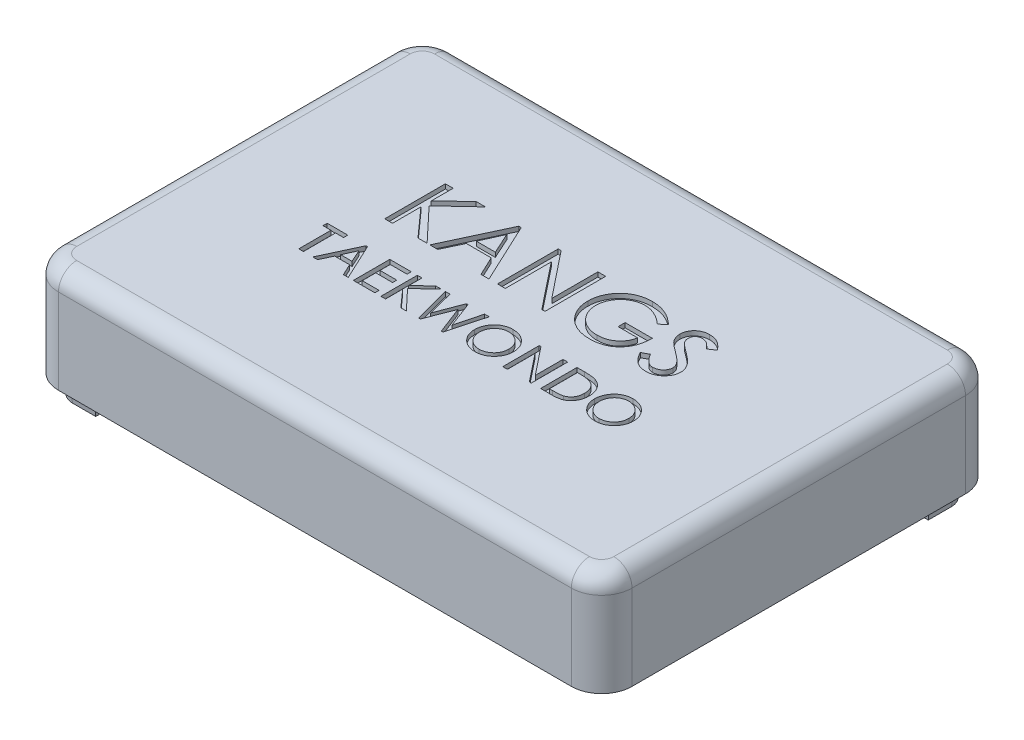
SolidWorks part; units mm, degrees
ref_plane "Front Plane" through (0, 0, 0) normal (0, 0, 1) x (1, 0, 0)
ref_plane "Top Plane" through (0, 0, 0) normal (0, 1, 0) x (1, 0, 0)
ref_plane "Right Plane" through (0, 0, 0) normal (1, 0, 0) x (0, 0, -1)
sketch "Sketch1" plane through (0, 0, 0) normal (0, 1, 0) x (1, 0, 0)
  line L0 (-44.1692, -23.3779) -> (-44.1692, 31.5679)
  line L1 (-39.1692, -26.3779) -> (45.3308, -26.3779)
  line L2 (-42.1692, -23.3779) -> (-42.1692, 31.5679)
  line L3 (-39.1692, 34.5679) -> (45.3308, 34.5679)
  line L4 (48.3308, -23.3779) -> (48.3308, 31.5679)
  line L5 (-42.1692, -26.3779) -> (48.3308, 34.5679) construction
  line L6 (-42.1692, 34.5679) -> (48.3308, -26.3779) construction
  line L7 (-39.1692, 36.5679) -> (45.3308, 36.5679)
  line L8 (50.3308, -23.3779) -> (50.3308, 31.5679)
  line L9 (-39.1692, -28.3779) -> (45.3308, -28.3779)
  line L10 (-44.1692, -5.0821) -> (-44.1692, -18.2821) construction
  line L11 (45.3308, 12.7179) -> (45.3308, 1.7179) construction
  line L12 (-9.4142, 36.5679) -> (3.8358, 36.5679) construction
  line L13 (-33.1692, -23.3779) -> (42.8308, -23.3779) construction
  arc A0 (45.3308, -26.3779) -> (48.3308, -23.3779) centre (45.3308, -23.3779) ccw
  arc A1 (-39.1692, -26.3779) -> (-42.1692, -23.3779) centre (-39.1692, -23.3779) cw
  arc A2 (-42.1692, 31.5679) -> (-39.1692, 34.5679) centre (-39.1692, 31.5679) cw
  arc A3 (45.3308, 34.5679) -> (48.3308, 31.5679) centre (45.3308, 31.5679) cw
  arc A4 (-44.1692, 31.5679) -> (-39.1692, 36.5679) centre (-39.1692, 31.5679) cw
  arc A5 (45.3308, 36.5679) -> (50.3308, 31.5679) centre (45.3308, 31.5679) cw
  arc A6 (45.3308, -28.3779) -> (50.3308, -23.3779) centre (45.3308, -23.3779) ccw
  arc A7 (-39.1692, -28.3779) -> (-44.1692, -23.3779) centre (-39.1692, -23.3779) cw
  point P0 (0, 0)
  dimension "D1" = 3
  dimension "D3" = 3
  dimension "D4" = 3
  dimension "D2" = 2
extrude "Boss-Extrude1" add sketch "Sketch1" along normal blind 1.5 contours A7 L9 A6 L8 A5 L7 A4 L0 L3 A3 L4 A0 L1 A1 L2 A2 | L3 A3 L4 A0 L1 A1 L2 A2 region at (-43.0226, 0, -4.095)
extrude "Boss-Extrude2" add sketch "Sketch1<3>" against normal up to surface (15.53 mm away)
sketch "Sketch1<3>" plane through (0, 0, 0) normal (0, 1, 0) x (1, 0, 0) same geometry as "Sketch1"
sketch "Sketch2" plane through (0, 0, -36.5679) normal (0, 0, -1) x (-1, 0, 0)
  line L5 (-34.8158, -2) -> (25.1542, -2)
  line L6 (-34.8158, -2) -> (-34.8158, -16.03)
  line L7 (-34.8158, -16.03) -> (25.1542, -16.03)
  line L30 (25.1542, -2) -> (25.1542, -16.03)
  line L36 (-21.0658, -3) -> (-34.3158, -3) construction
  line L37 (-34.3158, -15.53) -> (-34.3158, -3) construction
  line L40 (-21.0658, -15.53) -> (-34.3158, -15.53) construction
  line L41 (24.6542, -15.53) -> (24.6542, -3) construction
  dimension "D2" = 1
  dimension "D3" = 0.5
  dimension "D6" = 0.5
  dimension "D1" = 0.5
extrude "Cut-Extrude1" cut sketch "Sketch2" against normal up to next
sketch "Sketch3" plane through (0, 0, 0) normal (0, -1, 0) x (1, 0, 0)
  line L0 (-34.8337, -30.7679) -> (-38.3692, -27.2324)
  line L1 (-38.3692, 19.0424) -> (-34.8337, 22.5779)
  line L2 (40.9953, -30.7679) -> (44.5308, -27.2324)
  line L3 (45.3308, -34.7679) -> (40.9953, -34.7679)
  line L4 (40.9953, -34.7679) -> (40.9953, -30.7679)
  line L5 (48.5308, -31.5679) -> (48.5308, -27.2324)
  line L6 (48.5308, -27.2324) -> (44.5308, -27.2324)
  line L7 (-39.1692, -34.7679) -> (-34.8337, -34.7679)
  line L8 (-34.8337, -34.7679) -> (-34.8337, -30.7679)
  line L9 (-42.3692, -31.5679) -> (-42.3692, -27.2324)
  line L10 (-42.3692, -27.2324) -> (-38.3692, -27.2324)
  line L11 (-42.3692, 23.3779) -> (-42.3692, 19.0424)
  line L12 (-42.3692, 19.0424) -> (-38.3692, 19.0424)
  line L13 (-34.8337, 22.5779) -> (-34.8337, 26.5779)
  line L14 (-34.8337, 26.5779) -> (-39.1692, 26.5779)
  arc A0 (48.5308, -31.5679) -> (45.3308, -34.7679) centre (45.3308, -31.5679) cw
  arc A1 (45.3308, -34.5679) -> (48.3308, -31.5679) centre (45.3308, -31.5679) ccw construction
  arc A3 (-39.1692, -34.7679) -> (-42.3692, -31.5679) centre (-39.1692, -31.5679) cw
  arc A4 (-42.1692, -31.5679) -> (-39.1692, -34.5679) centre (-39.1692, -31.5679) ccw construction
  arc A5 (-42.3692, 23.3779) -> (-39.1692, 26.5779) centre (-39.1692, 23.3779) cw
  arc A6 (-39.1692, 26.3779) -> (-42.1692, 23.3779) centre (-39.1692, 23.3779) ccw construction
  point P27 (-39.0446, 27.1175)
  dimension "D1" = 0.2
  dimension "D2" = 5
  dimension "D3" = 4
extrude "Boss-Extrude3" add sketch "Sketch3" along normal up to surface (15.53 mm away) up to face at (3.4308, -15.53, -10.3896)
extrude "Boss-Extrude4" add sketch "Sketch3<3>" along normal blind 3 draft 10 from surface starting at face at (0.4882, -15.53, -10.6621)
sketch "Sketch3<3>" plane through (0, 0, 0) normal (0, -1, 0) x (1, 0, 0) same geometry as "Sketch3"
fillet "Fillet1" radius 3 22 edges at (-42.7047, 1.5, -35.1034) (-44.1692, 1.5, -4.095) (-42.7047, 1.5, 26.9134) (3.0808, 1.5, 28.3779) (48.8663, 1.5, 26.9134) (50.3308, 1.5, -4.095) (48.8663, 1.5, -35.1034) (3.0808, 1.5, -36.5679) (-42.1692, 0, -4.095) (3.0808, 0, -34.5679) (48.3308, 0, -1.9272) (47.4521, 0, 25.4992) (5.2486, 0, 26.3779) (-34.8337, 0, -32.6679) (-36.6014, 0, -29.0001) (-40.2692, 0, -27.2324) (-40.2692, 0, 19.0424) (-36.6014, 0, 20.8101) (-34.8337, 0, 24.4779) (46.4308, 0, -27.2324) (42.763, 0, -29.0001) (40.9953, 0, -32.6679)
sketch "Sketch4" plane through (0, -15.53, 0) normal (0, -1, 0) x (1, 0, 0)
  line L0 (45.3308, -36.5679) -> (34.8158, -36.5679) construction
  line L1 (37.9225, -36.5679) -> (43.7808, -36.5679)
  line L2 (37.9225, -36.5679) -> (37.9225, -27.9824)
  line L3 (37.9225, -27.9824) -> (43.7808, -27.9824)
  line L4 (43.7808, -36.5679) -> (43.7808, -27.9824)
  line L5 (43.2808, -34.5679) -> (43.2808, -24.2221) construction
  line L6 (44.5308, -27.2324) -> (40.9953, -30.7679) construction
  point P8 (43.7808, -27.9824)
  dimension "D1" = 0.5
extrude "Cut-Extrude2" cut sketch "Sketch4" along normal through all
sketch "Sketch5" plane through (0, 1.5, 0) normal (0, 1, 0) x (1, 0, 0)
  line L0 (-41.1692, 5.9404) -> (47.3308, 5.9404) construction
  line L1 (-41.1692, -5.4272) -> (47.3308, -5.4272) construction
  line L2 (-41.1692, 31.5679) -> (-41.1692, -23.3779) construction
  line L3 (47.3308, -23.3779) -> (47.3308, 31.5679) construction
  text T0 "KANGS" font "Century Gothic" height 10
  text T1 "TAEKWONDO" font "Century Gothic" height 6
  point P5 (-41.1692, 12.184)
  point P8 (47.3308, 12.0593)
  point P11 (47.3308, -7.3214)
  point P12 (-41.1692, -9.6208)
extrude "Cut-Extrude3" cut sketch "Sketch5" against normal blind 0.75
